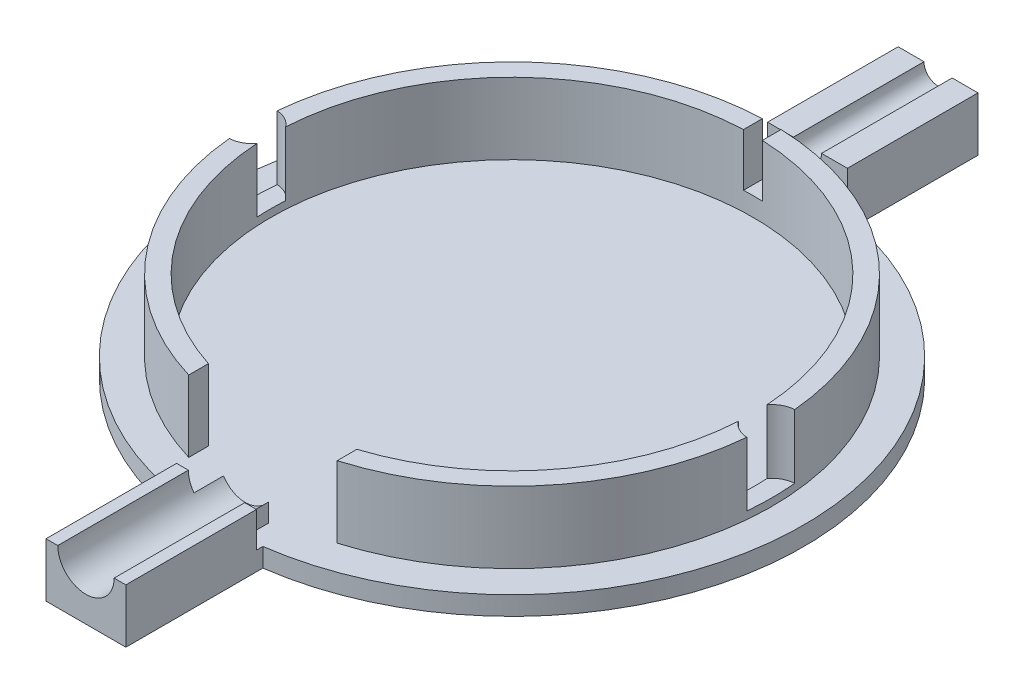
SolidWorks part; units mm, degrees
ref_plane "Front Plane" through (0, 0, 0) normal (0, 0, 1) x (1, 0, 0)
ref_plane "Top Plane" through (0, 0, 0) normal (0, 1, 0) x (1, 0, 0)
ref_plane "Right Plane" through (0, 0, 0) normal (1, 0, 0) x (0, 0, -1)
sketch "Sketch1" plane through (0, 0, 0) normal (0, 1, 0) x (1, 0, 0)
  circle A0 centre (0, 0) radius 31.06
  dimension "D1" = 62.12
extrude "Boss-Extrude1" add sketch "Sketch1" along normal blind 2
sketch "Sketch2" plane through (0, 2, 0) normal (0, 1, 0) x (1, 0, 0)
  circle A0 centre (0, 0) radius 27.66
  circle A1 centre (0, 0) radius 25.66
  circle A2 centre (0, 0) radius 31.06 construction
  dimension "D1" = 2
  dimension "D2" = 3.4
extrude "Boss-Extrude2" add sketch "Sketch2" along normal blind 7.6
sketch "Sketch4" plane through (0, 9.6, 0) normal (0, 1, 0) x (1, 0, 0)
  arc A0 (25.6148, -1.523) -> (27.5425, -2.5473) centre (27.66, 0) ccw
  circle A1 centre (0, 0) radius 27.66 construction
  arc A2 (-27.5425, -2.5473) -> (-25.6148, -1.523) centre (-27.66, 0) ccw
  circle A3 centre (0, 0) radius 25.66 construction
  arc A4 (-25.6148, 1.523) -> (-25.6148, -1.523) centre (0, 0) ccw
  arc A5 (-27.5425, 2.5473) -> (-27.5425, -2.5473) centre (0, 0) ccw
  arc A6 (25.6148, -1.523) -> (25.6148, 1.523) centre (0, 0) ccw
  arc A7 (27.5425, -2.5473) -> (27.5425, 2.5473) centre (0, 0) ccw
  arc A8 (-25.6148, 1.523) -> (-27.5425, 2.5473) centre (-27.66, 0) ccw
  arc A9 (27.5425, 2.5473) -> (25.6148, 1.523) centre (27.66, 0) ccw
  circle M1 centre (0, 0) radius 27.66
  circle M2 centre (0, 0) radius 25.66
  dimension "D1" = 5.1
  dimension "D2" = 5.1
extrude "Cut-Extrude1" cut sketch "Sketch4" against normal blind 6.8 contours A9 A0 M1 M2 | A4 A2 A5 A8 region at (26.7016, 9.6, 0)
sketch "Sketch5" plane through (0, 9.6, 0) normal (0, 1, 0) x (1, 0, 0)
  line L0 (0, -25.66) -> (0, -27.66)
  line L1 (3, -25.484) -> (3, -27.4968)
  line L2 (-3, -25.484) -> (-3, -27.4968)
  line L3 (3, -25.66) -> (3, -27.66) construction
  line L4 (-3, -25.66) -> (-3, -27.66) construction
  arc A0 (-25.6148, -1.523) -> (25.6148, -1.523) centre (0, 0) ccw construction
  arc A1 (-27.5425, -2.5473) -> (27.5425, -2.5473) centre (0, 0) ccw construction
  arc A3 (-3, -25.484) -> (3, -25.484) centre (0, 0) ccw
  arc A4 (-3, -27.4968) -> (3, -27.4968) centre (0, 0) ccw
  arc M2 (-27.5425, -2.5473) -> (27.5425, -2.5473) centre (0, 0) ccw
  arc M4 (25.6148, -1.523) -> (-25.6148, -1.523) centre (0, 0) cw
  dimension "D1" = 3
  dimension "D2" = 3
extrude "Cut-Extrude2" cut sketch "Sketch5" against normal blind 6.8 contours L2 L0 M4 M2 | L1 L0 M4 M2 region at (1.5016, 9.6, 26.6035) region at (-1.5016, 9.6, 26.6035)
sketch "Sketch7" plane through (0, 2, 0) normal (0, 1, 0) x (1, 0, 0)
  line L2 (2.4, -28.3014) -> (2.4, -30.9671)
  line L3 (-2.4, -28.3014) -> (-2.4, -30.9671)
  line L4 (3, -25.484) -> (3, -27.4968) construction
  circle A0 centre (0, 0) radius 31.06 construction
  arc A1 (-2.4, -30.9671) -> (2.4, -30.9671) centre (0, 0) ccw
  arc A4 (-2.4, -28.3014) -> (2.4, -28.3014) centre (0, 0.0572) ccw
  dimension "D1" = 4.8
  dimension "D2" = 0.6
extrude "Boss-Extrude5" add sketch "Sketch7" along normal blind 7.6
ref_plane "Plane1" through (0, 0, 31.06) normal (0, 0, 1) x (1, 0, 0)
sketch "Sketch8" plane through (0, 0, 31.06) normal (0, 0, 1) x (1, 0, 0)
  line L0 (2.4, 9.6) -> (-2.4, 9.6) construction
  line L1 (2.4, 9.6) -> (-2.4, 9.6)
  line L2 (31.06, 2) -> (-31.06, 2) construction
  line L3 (2.4, 2) -> (-2.4, 2)
  line L4 (2.4, 9.6) -> (2.4, 2) construction
  line L5 (2.4, 9.6) -> (2.4, 2)
  line L6 (-2.4, 9.6) -> (-2.4, 2) construction
  line L7 (-2.4, 9.6) -> (-2.4, 2)
  line L8 (-2.4, 5.75) -> (2.4, 5.75)
  circle A0 centre (0, 5.75) radius 3
  dimension "D2" = 6
  dimension "D1" = 3.75
extrude "Cut-Extrude3" cut sketch "Sketch8" against normal blind 7.6 contours L7 A0 L5 L8 | L5 A0 L7 L8 | A0 L5 L1 L7 region at (0, 8.9459, 31.06) region at (0, 7.0916, 31.06) region at (0, 4.4084, 31.06)
sketch "Sketch9" plane through (0, 0, 0) normal (0, 0, 1) x (1, 0, 0)
  line L0 (25.6148, 9.6) -> (-25.6148, 9.6) construction
  line L1 (-1, 4) -> (1, 4)
  line L2 (-1, 4) -> (-1, 9.6)
  line L3 (-1, 6) -> (1, 6)
  line L4 (1, 4) -> (1, 9.6)
  line L5 (-1, 4) -> (1, 6) construction
  line L6 (-1, 6) -> (1, 4) construction
  line L7 (1, 9.6) -> (-1, 9.6)
  point P0 (0, 5)
  dimension "D1" = 5
  dimension "D2" = 2
  dimension "D3" = 2
extrude "Cut-Extrude4" cut sketch "Sketch9" against normal through all contours L1 L4 L3 L2 | L4 L7 L2 L3 region at (0, 5, 0) region at (0, 7.8, 0)
sketch "Sketch11" plane through (0, 9.6, 0) normal (0, 1, 0) x (1, 0, 0)
  line L2 (-7.9, -27.9874) -> (7.9, -27.9874)
  line L4 (7.9, -24.1658) -> (-7.9, -24.1658)
  line L5 (7.9, -24.1658) -> (7.9, -28.7542)
  line L6 (7.9, -28.7542) -> (-7.9, -28.7542)
  line L7 (-7.9, -24.1658) -> (-7.9, -28.7542)
  line L8 (7.9, -24.1658) -> (-7.9, -28.7542) construction
  line L9 (7.9, -28.7542) -> (-7.9, -24.1658) construction
  arc A2 (3, -25.484) -> (25.6148, -1.523) centre (0, 0) ccw construction
  arc A3 (3, -25.484) -> (25.6148, -1.523) centre (0, 0) ccw
  point P7 (0, -26.46)
  line M1 (-3, -27.4968) -> (-3, -25.484)
  arc M2 (-3, -25.484) -> (-25.6148, -1.523) centre (0, 0) cw
  arc M4 (-27.5425, -2.5473) -> (-3, -27.4968) centre (0, 0) ccw
  dimension "D1" = 15.8
extrude "Cut-Extrude5" cut sketch "Sketch11" against normal up to surface (7.6 mm away) contours A3 | L4 L7 L2 L5 M2 M1 M4 | L7 M2 M4 M1 region at (1.0887, 9.6, 26.0814) region at (-5.4661, 9.6, 26.0526) up to face at (0, 2, 27.66)
sketch "Sketch12" plane through (0, 0, 0) normal (0, -1, 0) x (1, 0, 0)
  line L0 (0, 31.06) -> (0, 45.35)
  line L1 (-4.25, 31.06) -> (4.25, 31.06)
  line L2 (4.25, 30.7679) -> (4.25, 45.35)
  line L3 (-4.25, 30.7679) -> (-4.25, 45.35)
  line L4 (-4.25, 45.35) -> (4.25, 45.35)
  line L5 (5.5481, 0) -> (-4.25, 0)
  line L6 (-14.4841, 45.35) -> (8.5, 45.35) construction
  line L7 (-14.4841, 31.06) -> (8.5, 31.06) construction
  line L8 (-4.25, -45.35) -> (4.25, -45.35)
  line L9 (-4.25, -30.7679) -> (-4.25, -45.35)
  line L10 (4.25, -30.7679) -> (4.25, -45.35)
  line L11 (-4.25, -31.06) -> (4.25, -31.06)
  line L12 (0, -31.06) -> (0, -45.35)
  circle A0 centre (0, 0) radius 31.06 construction
  circle A1 centre (0, 0) radius 31.06
  point P6 (4.25, 0)
  point P8 (-4.25, 0)
  circle M1 centre (0, 0) radius 31.06
  dimension "D1" = 14.29
  dimension "D5" = 14.29
extrude "Boss-Extrude7" add sketch "Sketch12" against normal blind 2 contours L4 L0 L1 L2 | L4 L3 L1 L0 | L2 L1 M1 | L3 L1 M1 | L11 L12 L8 L10 | L12 L11 L9 L8 | L9 L11 M1 | L11 L10 M1 region at (-2.125, 0, 38.205) region at (-3.1885, 0, 30.9724) region at (2.125, 0, 38.205) region at (3.1885, 0, 30.9724) region at (-3.1885, 0, -30.9724) region at (3.1885, 0, -30.9724) region at (-2.125, 0, -38.205) region at (2.125, 0, -38.205)
sketch "Sketch13" plane through (0, 0, 45.35) normal (0, 0, 1) x (1, 0, 0)
  line L0 (-4.25, 2) -> (4.25, 2) construction
  line L1 (-4.25, 2) -> (4.25, 2)
  line L2 (-3, 5.75) -> (-4.25, 5.75)
  line L3 (4.25, 2) -> (-4.25, 2)
  line L4 (4.25, 2) -> (4.25, 5.75)
  line L5 (4.25, 5.75) -> (3, 5.75)
  line L6 (-4.25, 2) -> (-4.25, 5.75)
  arc A0 (-3, 5.75) -> (3, 5.75) centre (0, 5.75) ccw
  dimension "D2" = 6
  dimension "D1" = 3.75
extrude "Boss-Extrude8" add sketch "Sketch13" against normal blind 13.9 contours L3 L6 L2 A0 L5 L4
sketch "Sketch14" plane through (0, 0, 31.06) normal (0, 0, 1) x (1, 0, 0)
  line L3 (-2.4, 2) -> (2.4, 2)
  line L4 (2.4, 2) -> (2.4, 3.95)
  line L5 (-2.4, 3.95) -> (-2.4, 2)
  line L6 (-2.4, 2) -> (2.4, 2)
  line L7 (2.4, 2) -> (2.4, 3.95)
  line L8 (-2.4, 3.95) -> (-2.4, 2)
  arc A1 (-2.4, 3.95) -> (2.4, 3.95) centre (0, 5.75) ccw
  arc A2 (-2.4, 3.95) -> (2.4, 3.95) centre (0, 5.75) ccw
  dimension "D1" = 0
extrude "Boss-Extrude9" add sketch "Sketch14" along normal blind 2 and the other way blind 2
sketch "Sketch15" plane through (0, 0, -45.35) normal (0, 0, -1) x (-1, 0, 0)
  line L0 (-1.5, 5.75) -> (-4.25, 5.75)
  line L1 (4.25, 0) -> (-4.25, 0)
  line L2 (4.25, 0) -> (4.25, 5.75)
  line L3 (4.25, 5.75) -> (1.5, 5.75)
  line L4 (-4.25, 0) -> (-4.25, 5.75)
  arc A0 (-1.5, 5.75) -> (1.5, 5.75) centre (0, 5.75) ccw
  dimension "D2" = 3
  dimension "D1" = 5.75
extrude "Boss-Extrude10" add sketch "Sketch15" against normal blind 13.9
